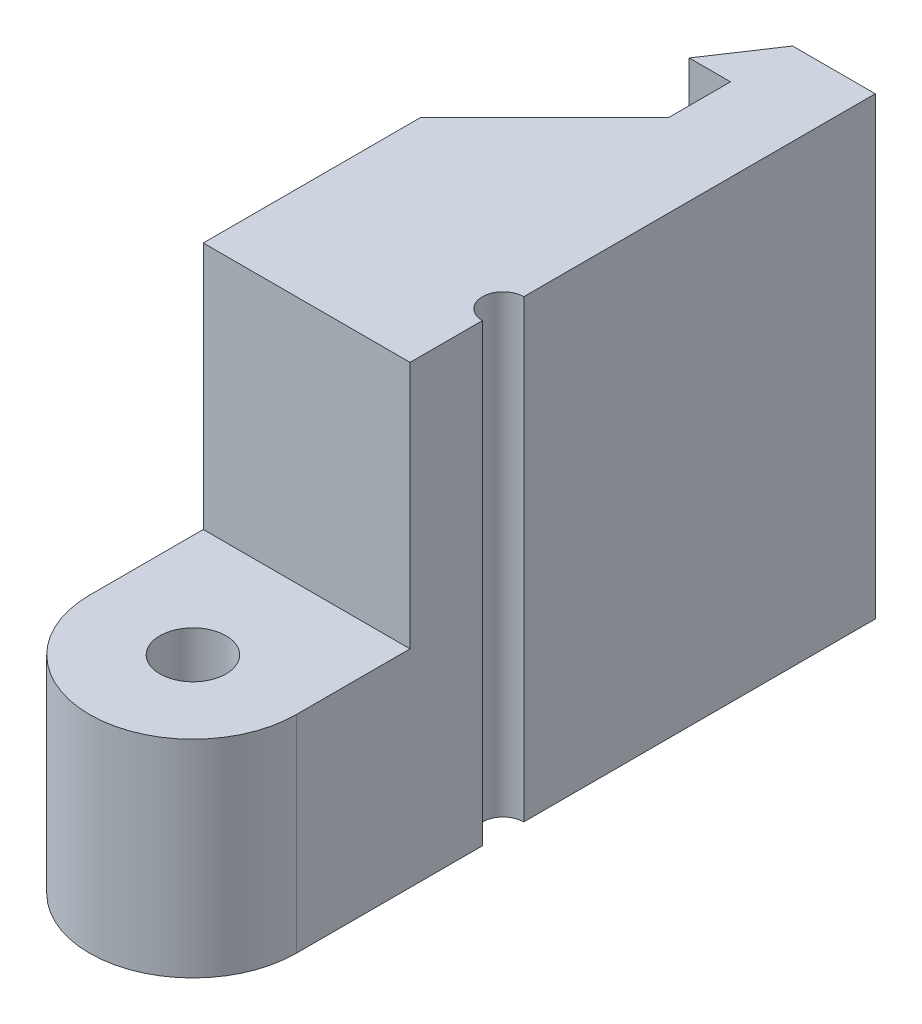
SolidWorks part; units mm, degrees
ref_plane "Front Plane" through (0, 0, 0) normal (0, 0, 1) x (1, 0, 0)
ref_plane "Top Plane" through (0, 0, 0) normal (0, 1, 0) x (1, 0, 0)
ref_plane "Right Plane" through (0, 0, 0) normal (1, 0, 0) x (0, 0, -1)
sketch "Sketch1" plane through (0, 0, 0) normal (0, 1, 0) x (1, 0, 0)
  line L0 (0, 0) -> (0, 43.6303) construction
  line L1 (-5, 0) -> (-5, 43.6303)
  line L2 (5, 0) -> (5, 9)
  line L3 (5, 11) -> (5, 43.6303)
  line L4 (-5, 20) -> (5, 20) construction
  line L5 (-5, 22) -> (5, 22)
  arc A0 (-5, 0) -> (5, 0) centre (0, 0) ccw
  arc A1 (5, 43.6303) -> (-5, 43.6303) centre (0, 43.6303) ccw
  circle A2 centre (0, 0) radius 1.6
  arc A3 (5, 11) -> (5, 9) centre (5, 10) ccw
  circle A4 centre (5, 10) radius 39 construction
  circle A5 centre (0, 15) radius 1.75 construction
  dimension "D1" = 3.2
  dimension "D2" = 2
  dimension "D4" = 5
  dimension "D6" = 78
  dimension "D8" = 3.5
  dimension "D10" = 7
  dimension "D3" = 0
  dimension "D5" = 10
  dimension "D7" = 10
  dimension "D9" = 5
extrude "Boss-Extrude1" add sketch "Sketch1" along normal blind 10 contours A3 L3 L5 L1 A0 L2 A2 region at (-0.0288, 0, -9.2966)
sketch "Sketch2" plane through (5, 0, 0) normal (1, 0, 0) x (0, 0, -1)
  line L0 (10, 0) -> (10, 10) construction
  line L1 (10, 5) -> (20, 5)
  line L4 (9, 0) -> (11, 0)
  line L5 (11, 0) -> (11, 10)
  line L6 (9, 0) -> (11, 0)
  line L7 (9, 10) -> (9, 0)
  line L9 (11, 0) -> (11, 10) construction
  line L11 (9, 10) -> (9, 0) construction
  line L14 (11, 10) -> (9, 10)
  line L15 (11, 10) -> (9, 10)
  circle A0 centre (20, 5) radius 2.5
  dimension "D2" = 5
  dimension "D3" = 10
  dimension "D1" = 0
extrude "Cut-Extrude1" [suppressed] cut sketch "Sketch2" against normal through all contours A0
sketch "Sketch3" plane through (0, 10, 0) normal (0, 1, 0) x (1, 0, 0)
  line L0 (-5, 0) -> (-5, 22) construction
  line L1 (5, 5.5) -> (-5, 5.5)
  line L2 (5, 5.5) -> (5, 9)
  line L3 (5, 22) -> (-5, 22)
  line L4 (-5, 5.5) -> (-5, 22)
  line L5 (5, 11) -> (5, 22)
  line L6 (-5, 22) -> (5, 22) construction
  line L8 (5, 11) -> (5, 22) construction
  circle A0 centre (0, 0) radius 5.5 construction
  arc A2 (5, 11) -> (5, 9) centre (5, 10) ccw
  arc A3 (5, 11) -> (5, 9) centre (5, 10) ccw construction
  dimension "D1" = 11
extrude "Boss-Extrude2" add sketch "Sketch3" along normal blind 12
ref_plane "Plane1" through (0, 0, -55) normal (0, 0, 1) x (1, 0, 0)
sketch "Sketch4" plane through (0, 0, -55) normal (0, 0, 1) x (1, 0, 0)
  line L0 (0, 0) -> (0, 5) construction
  line L1 (0, 5) -> (-5, 5) construction
  line L2 (-5, 10) -> (-5, 0) construction
  line L3 (-5, 5) -> (0, 5)
  circle A0 centre (0, 5) radius 2
  dimension "D1" = 4
extrude "Cut-Extrude2" [suppressed] cut sketch "Sketch4" along normal blind 25 contours A0
sketch "Sketch5" plane through (0, 22, 0) normal (0, 1, 0) x (1, 0, 0)
  line L0 (5, 22) -> (5, 28)
  line L1 (5, 28) -> (1, 28)
  line L2 (1, 28) -> (-1, 25)
  line L3 (-1, 25) -> (1, 25)
  line L4 (1, 25) -> (1, 22)
  line L5 (5, 22) -> (-5, 22) construction
  line L6 (1, 22) -> (5, 22)
  dimension "D1" = 3
  dimension "D2" = 4
  dimension "D3" = 3
  dimension "D4" = 2
extrude "Boss-Extrude3" add sketch "Sketch5" against normal up to surface (22 mm away) up to face at (1.5, 0, -9.8333)
chamfer "Chamfer1" distance 6 angle 45 1 edges at (-5, 11, -22)
